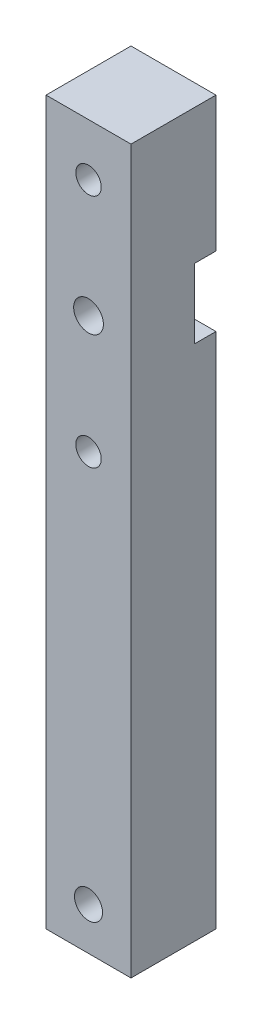
SolidWorks part; units mm, degrees
ref_plane "Front" through (0, 0, 0) normal (0, 0, 1) x (1, 0, 0)
ref_plane "Top" through (0, 0, 0) normal (0, 1, 0) x (1, 0, 0)
ref_plane "Right" through (0, 0, 0) normal (1, 0, 0) x (0, 0, -1)
sketch "Sketch1" plane through (0, 0, 0) normal (0, 1, 0) x (1, 0, 0)
  line L1 (0, 0) -> (10, 0)
  line L2 (0, 0) -> (0, 10)
  line L3 (0, 10) -> (10, 10)
  line L4 (10, 0) -> (10, 10)
  dimension "D1" = 10
  dimension "D2" = 10
extrude "Boss-Extrude1" add sketch "Sketch1" along normal blind 85
sketch "Sketch2" plane through (0, 0, -10) normal (0, 0, -1) x (-1, 0, 0)
  line L0 (-5, 85) -> (-5, 65)
  line L1 (-10, 85) -> (0, 85) construction
  line L2 (-10, 85) -> (-10, 0) construction
  line L3 (0, 69.1) -> (-10, 69.1)
  line L4 (0, 69.1) -> (0, 60.9)
  line L5 (0, 60.9) -> (-10, 60.9)
  line L6 (-10, 69.1) -> (-10, 60.9)
  line L7 (0, 69.1) -> (-10, 60.9) construction
  line L8 (0, 60.9) -> (-10, 69.1) construction
  line M4 (0, 0) -> (0, 85)
  line M6 (-10, 85) -> (-10, 0)
  dimension "D1" = 20
  dimension "D2" = 8.2
extrude "Cut-Extrude1" cut sketch "Sketch2" against normal blind 2.5 contours L5 L3 M4 M6 region at (0.1293, 65, -10)
sketch "Sketch3" plane through (0, 0, -7.5) normal (0, 0, -1) x (-1, 0, 0)
  line L0 (0, 65) -> (-10, 65)
  line L1 (0, 60.9) -> (0, 69.1) construction
  line L2 (-10, 69.1) -> (-10, 60.9) construction
  circle A0 centre (-5, 65) radius 1.75
extrude "Cut-Extrude2" cut sketch "Sketch3" against normal through all contours L0 A0 | L0 A0 region at (5, 64.2573, -7.5) region at (5, 65.7427, -7.5)
sketch "Sketch4" plane through (0, 0, -7.5) normal (0, 0, -1) x (-1, 0, 0)
  line L0 (-5, 65) -> (-5, 78.856)
  line L1 (-5, 65) -> (-5, 51.144)
  circle A0 centre (-5, 78.856) radius 1.5
  circle A1 centre (-5, 51.144) radius 1.5
  dimension "D2" = 13.856
  dimension "D1" = 13.856
extrude "Cut-Extrude3" cut sketch "Sketch4" against normal through all and the other way blind 2.5 contours A0 | A1
sketch "Sketch5" plane through (0, 0, 0) normal (0, 0, 1) x (1, 0, 0)
  line L0 (5, 0) -> (5, 5)
  line L1 (0, 0) -> (10, 0) construction
  circle A0 centre (5, 5) radius 1.65
  circle A2 centre (5, 15) radius 1.65
  circle A3 centre (5, 25) radius 1.65
  dimension "D1" = 5
  dimension "D2" = 3
extrude "Cut-Extrude4" cut sketch "Sketch5" against normal through all contours A0
